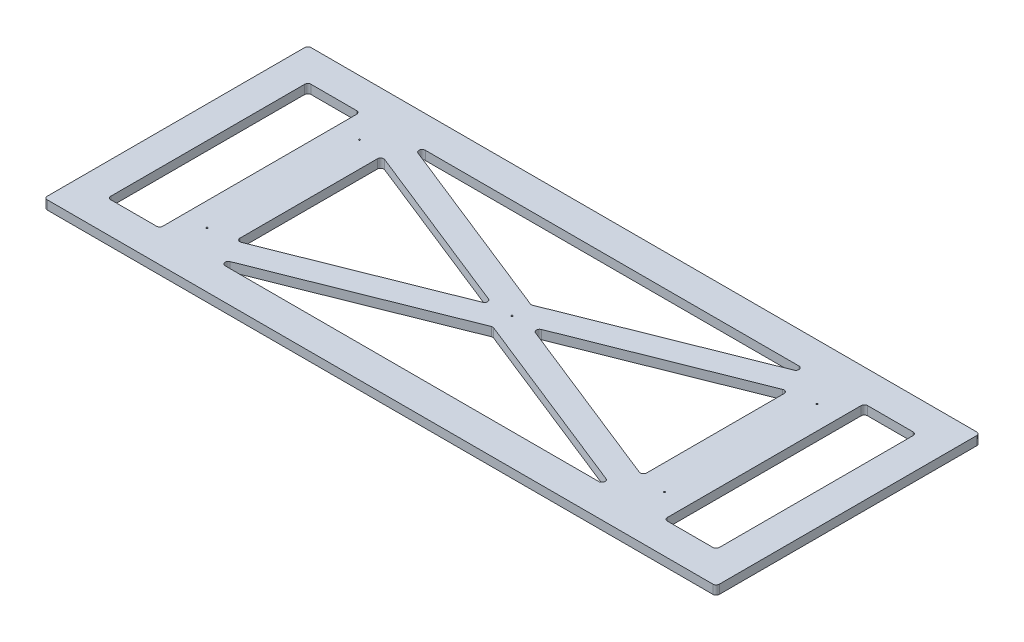
SolidWorks part; units mm, degrees
ref_plane "Front Plane" through (0, 0, 0) normal (0, 0, 1) x (1, 0, 0)
ref_plane "Top Plane" through (0, 0, 0) normal (0, 1, 0) x (1, 0, 0)
ref_plane "Right Plane" through (0, 0, 0) normal (1, 0, 0) x (0, 0, -1)
sketch "Sketch1" plane through (0, 0, 0) normal (0, 1, 0) x (1, 0, 0)
  line L1 (-671.5125, 263.525) -> (671.5125, 263.525)
  line L2 (-671.5125, 263.525) -> (-671.5125, -263.525)
  line L3 (-671.5125, -263.525) -> (671.5125, -263.525)
  line L4 (671.5125, 263.525) -> (671.5125, -263.525)
  line L5 (-671.5125, 263.525) -> (671.5125, -263.525) construction
  line L6 (-671.5125, -263.525) -> (671.5125, 263.525) construction
  point P0 (0, 0)
  dimension "D1" = 527.05
  dimension "D2" = 1343.025
extrude "Boss-Extrude1" add sketch "Sketch1" along normal blind 17.78
fillet "Fillet1" radius 6.35 4 edges at (-671.5125, 8.89, 263.525) (-671.5125, 8.89, -263.525) (671.5125, 8.89, -263.525) (671.5125, 8.89, 263.525)
hole_wizard "1/8 (0.125) Diameter Hole1" positions "Sketch3" profile "Sketch4" hole size "1/8" standard "ANSI Inch" end condition through all
sketch "Sketch3" plane through (0, 17.78, 0) normal (0, 1, 0) x (1, 0, 0)
  line L1 (-457.2, -152.4) -> (457.2, -152.4) construction
  line L2 (-457.2, -152.4) -> (-457.2, 152.4) construction
  line L3 (-457.2, 152.4) -> (457.2, 152.4) construction
  line L4 (457.2, -152.4) -> (457.2, 152.4) construction
  line L5 (-457.2, -152.4) -> (457.2, 152.4) construction
  line L6 (-457.2, 152.4) -> (457.2, -152.4) construction
  point P0 (0, 0)
  point P1 (457.2, 152.4)
  point P32 (-457.2, -152.4)
  point P33 (-457.2, 152.4)
  point P34 (457.2, -152.4)
  dimension "D1" = 914.4
  dimension "D2" = 304.8
sketch "Sketch4" plane through (0, 17.78, 0) normal (1, 0, 0) x (0, 0, 1)
  line L0 (0, 0) -> (0, 17.78)
  line L1 (0, 17.78) -> (1.5875, 17.78)
  line L2 (1.5875, 17.78) -> (1.5875, 0)
  line L5 (1.5875, 0) -> (0, 0)
  line L11 (0, -6.35) -> (0, 107.95) construction
  dimension "Thru Hole Dia." = 3.175
  dimension "Thru Hole Depth" = 17.78
sketch "Sketch2" plane through (0, 17.78, 0) normal (0, 1, 0) x (1, 0, 0)
  line L1 (-635, -330.2) -> (635, -330.2)
  line L2 (-635, -330.2) -> (-635, 330.2)
  line L3 (-635, 330.2) -> (635, 330.2)
  line L4 (635, -330.2) -> (635, 330.2)
  line L5 (-635, -330.2) -> (635, 330.2) construction
  line L6 (-635, 330.2) -> (635, -330.2) construction
  point P0 (0, 0)
  dimension "D1" = 660.4
  dimension "D2" = 1270
extrude "Boss-Extrude2" [suppressed] add sketch "Sketch2" along normal blind 9.525
sketch "Sketch5" plane through (0, 17.78, 0) normal (0, 1, 0) x (1, 0, 0)
  line L0 (-406.4, 200.025) -> (406.4, 200.025)
  line L1 (665.1625, 263.525) -> (-665.1625, 263.525) construction
  line L2 (0, 38.1) -> (-406.4, 200.025)
  line L3 (406.4, 200.025) -> (0, 38.1)
  line L4 (0, 263.525) -> (0, -263.525) construction
  line L5 (-665.1625, -263.525) -> (665.1625, -263.525) construction
  line L6 (-671.5125, 0) -> (671.5125, 0) construction
  line L7 (-671.5125, 257.175) -> (-671.5125, -257.175) construction
  line L8 (671.5125, -257.175) -> (671.5125, 257.175) construction
  line L9 (0, -38.1) -> (-406.4, -200.025)
  line L10 (-406.4, -200.025) -> (406.4, -200.025)
  line L11 (406.4, -200.025) -> (0, -38.1)
  line L12 (406.4, 146.7445) -> (406.4, -146.7445)
  line L13 (406.4, -146.7445) -> (38.1, 0)
  line L14 (406.4, 146.7445) -> (38.1, 0)
  line L15 (-406.4, 146.7445) -> (-38.1, 0)
  line L16 (-406.4, 146.7445) -> (-406.4, -146.7445)
  line L17 (-406.4, -146.7445) -> (-38.1, 0)
  line L18 (608.0125, -200.025) -> (504.1452, -200.025)
  line L19 (-608.0125, -200.025) -> (-504.1452, -200.025)
  line L20 (-608.0125, -200.025) -> (-608.0125, 200.025)
  line L21 (-608.0125, 200.025) -> (-504.1452, 200.025)
  line L22 (-504.1452, -200.025) -> (-504.1452, 200.025)
  line L23 (-608.0125, -200.025) -> (-504.1452, 200.025) construction
  line L24 (-608.0125, 200.025) -> (-504.1452, -200.025) construction
  line L25 (608.0125, -200.025) -> (608.0125, 200.025)
  line L26 (608.0125, 200.025) -> (504.1452, 200.025)
  line L27 (504.1452, -200.025) -> (504.1452, 200.025)
  circle A0 centre (0, 0) radius 38.1 construction
  point P3 (0, 200.025)
  point P30 (-556.0789, 0)
  dimension "D2" = 76.2
  dimension "D4" = 115.4336
  dimension "D1" = 63.5
  dimension "D3" = 812.8
  dimension "D5" = 63.5
extrude "Cut-Extrude1" cut sketch "Sketch5" against normal through all
fillet "Fillet2" radius 6.35 20 edges at (504.1452, 8.89, -200.025) (504.1452, 8.89, 200.025) (608.0125, 8.89, 200.025) (406.4, 8.89, 146.7445) (406.4, 8.89, 200.025) (608.0125, 8.89, -200.025) (406.4, 8.89, -146.7445) (406.4, 8.89, -200.025) (38.1, 8.89, 0) (0, 8.89, 38.1) (0, 8.89, -38.1) (-38.1, 8.89, 0) (-406.4, 8.89, 200.025) (-406.4, 8.89, -200.025) (-406.4, 8.89, -146.7445) (-406.4, 8.89, 146.7445) (-608.0125, 8.89, 200.025) (-504.1452, 8.89, 200.025) (-504.1452, 8.89, -200.025) (-608.0125, 8.89, -200.025)
